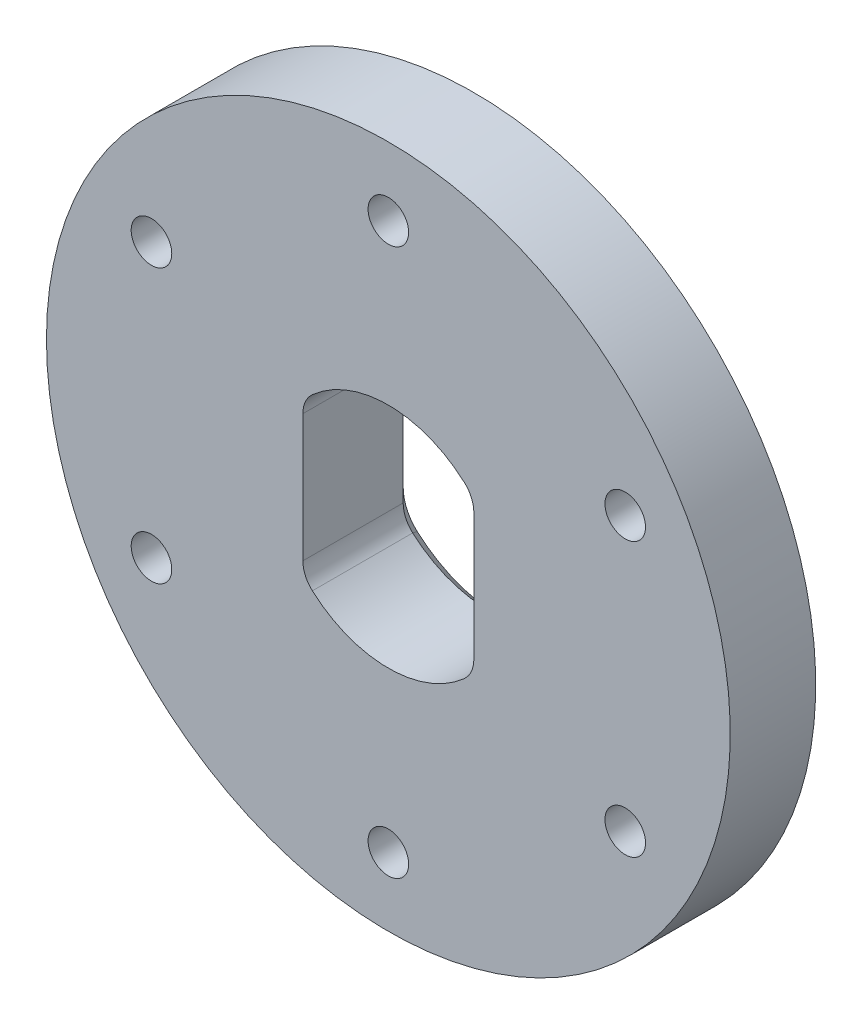
SolidWorks part; units mm, degrees
material "7075-T6, Plate (SS)"
ref_plane "Front Plane" through (0, 0, 0) normal (0, 0, 1) x (1, 0, 0)
ref_plane "Top Plane" through (0, 0, 0) normal (0, 1, 0) x (1, 0, 0)
ref_plane "Right Plane" through (0, 0, 0) normal (1, 0, 0) x (0, 0, -1)
sketch "Sketch1" plane through (0, 0, 0) normal (0, 0, 1) x (1, 0, 0)
  circle A0 centre (0, 0) radius 19.05
  dimension "D1" = 38.1
extrude "Boss-Extrude1" add sketch "Sketch1" along normal blind 4.7625
sketch "Sketch2" plane through (0, 0, 0) normal (0, 0, -1) x (-1, 0, 0)
  circle A0 centre (0, 0) radius 11.1125
  dimension "D1" = 22.225
extrude "Boss-Extrude2" add sketch "Sketch2" along normal blind 1.5875
fillet "Fillet1" radius 1.5875 1 edges at (11.1125, 0, 0)
sketch "Sketch3" plane through (0, 0, -1.5875) normal (0, 0, -1) x (-1, 0, 0)
  line L0 (-4.7625, 4.2001) -> (-4.7625, -4.2001)
  line L1 (4.7625, 4.2001) -> (4.7625, -4.2001)
  arc A0 (4.7625, 4.2001) -> (-4.7625, 4.2001) centre (0, 0) ccw
  arc A1 (-4.7625, -4.2001) -> (4.7625, -4.2001) centre (0, 0) ccw
  dimension "D1" = 12.7
  dimension "D2" = 4.7625
  dimension "D3" = 4.7625
extrude "Cut-Extrude1" cut sketch "Sketch3" against normal through all
fillet "Fillet2" radius 1.5875 4 edges at (-4.7625, -4.2001, 1.5875) (4.7625, -4.2001, 1.5875) (-4.7625, 4.2001, 1.5875) (4.7625, 4.2001, 1.5875)
hole_wizard "#4-40 Tapped Hole1" positions "Sketch5" profile "Sketch6" tap size "#4-40" standard "Ansi Inch" end condition up to next
sketch "Sketch5" plane through (0, 0, 4.7625) normal (0, 0, 1) x (1, 0, 0)
  point P0 (0, 15.24)
  dimension "D1" = 15.24
sketch "Sketch6" plane through (0, 15.24, 4.7625) normal (1, 0, 0) x (0, -1, 0)
  line L0 (0, 0) -> (0, 4.7635)
  line L1 (0, 4.7635) -> (1.1303, 4.7635)
  line L2 (1.1303, 4.7635) -> (1.1303, 0)
  line L5 (1.1303, 0) -> (0, 0)
  line L11 (0, -6.35) -> (0, 107.95) construction
  dimension "Thru Tap Drill Dia." = 2.2606
  dimension "Thru Tap Drill Depth" = 4.7635
cosmetic thread "Hole Thread1" parameters "D2"=2.8448
pattern_circular "CirPattern1" count 6 over 360 about axis through (0, 0, 4.7625) along (0, 0, 1) of "#4-40 Tapped Hole1"
chamfer "Chamfer1" distance 0.762 angle 45 8 edges at (0, -6.35, -1.5875) (-4.6242, -4.1979, -1.5875) (4.6242, -4.1979, -1.5875) (-4.7625, 0, -1.5875) (4.7625, 0, -1.5875) (-4.6242, 4.1979, -1.5875) (4.6242, 4.1979, -1.5875) (0, 6.35, -1.5875)
